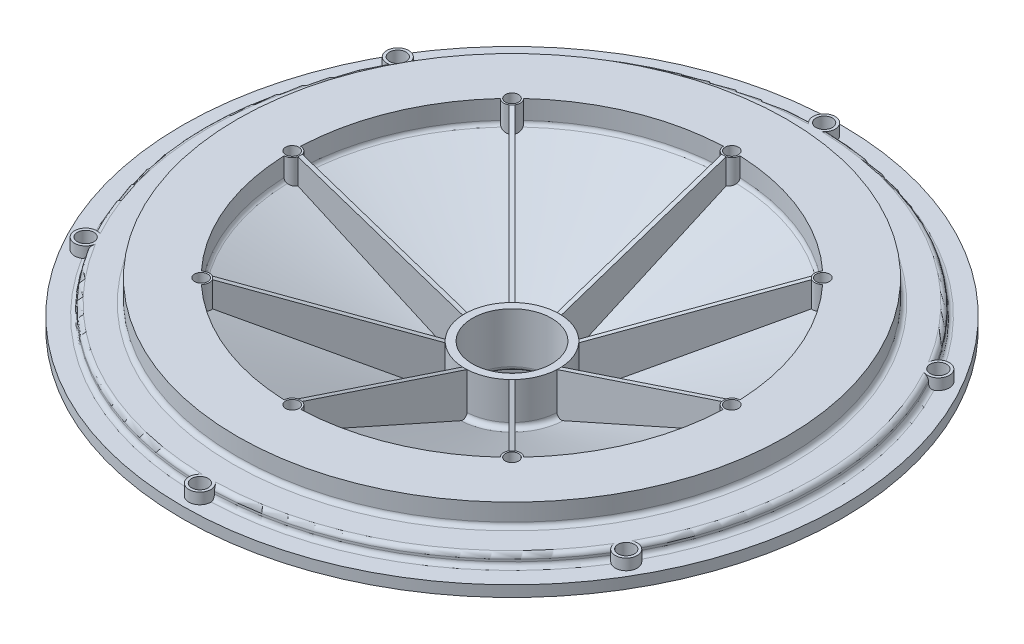
SolidWorks part; units mm, degrees
ref_plane "Front Plane" through (0, 0, 0) normal (0, 0, 1) x (1, 0, 0)
ref_plane "Top Plane" through (0, 0, 0) normal (0, 1, 0) x (1, 0, 0)
ref_plane "Right Plane" through (0, 0, 0) normal (1, 0, 0) x (0, 0, -1)
sketch "Sketch4" plane through (0, 0, 0) normal (0, 0, 1) x (1, 0, 0)
  line L0 (0, 0) -> (1.8, 0) construction
  line L1 (1.8, 2.5) -> (1.8, 0.22)
  line L2 (2, 0.02) -> (4.35, 0.02)
  line L3 (4.55, -0.18) -> (4.55, -1.95)
  line L4 (4.35, -2.15) -> (2.15, -2.15)
  line L5 (2.15, -2.15) -> (2.15, -2.3)
  line L6 (2.35, -2.5) -> (4.9, -2.5)
  line L7 (4.9, -2.5) -> (4.9, -1.2585)
  line L8 (0, 0) -> (0, 10.2137) construction
  line L9 (4.9, -1.2585) -> (4.9, 1.0489)
  line L10 (5.0186, 1.2315) -> (10.4, 3.6309)
  line L11 (1.8, 2.5) -> (2.15, 2.5)
  line L12 (2.15, 2.5) -> (2.15, 0.8082)
  line L13 (2.4314, 0.6255) -> (9.8814, 3.9471)
  line L14 (10, 4.1298) -> (10, 4.99)
  line L15 (10, 4.99) -> (12.5, 4.99)
  line L16 (12.5, 4.99) -> (12.5, 4.2)
  line L17 (12.7, 4) -> (13.8, 4)
  line L18 (14, 3.8) -> (14, 3.7)
  line L19 (14.2, 3.5) -> (15, 3.5)
  line L22 (13.5, 3) -> (13.5, 3.4309)
  line L23 (13.3, 3.6309) -> (10.4, 3.6309)
  line L24 (13.5, 3) -> (15, 3)
  line L25 (15, 3.5) -> (15, 3)
  arc A0 (2.15, 0.8082) -> (2.4314, 0.6255) centre (2.35, 0.8082) ccw
  arc A1 (4.9, 1.0489) -> (5.0186, 1.2315) centre (5.1, 1.0489) cw
  arc A2 (9.8814, 3.9471) -> (10, 4.1298) centre (9.8, 4.1298) ccw
  arc A3 (14, 3.7) -> (14.2, 3.5) centre (14.2, 3.7) ccw
  arc A4 (13.5, 3.4309) -> (13.3, 3.6309) centre (13.3, 3.4309) ccw
  arc A5 (13.8, 4) -> (14, 3.8) centre (13.8, 3.8) cw
  arc A6 (12.5, 4.2) -> (12.7, 4) centre (12.7, 4.2) ccw
  arc A7 (2.15, -2.3) -> (2.35, -2.5) centre (2.35, -2.3) ccw
  arc A8 (1.8, 0.22) -> (2, 0.02) centre (2, 0.22) ccw
  arc A9 (4.55, -1.95) -> (4.35, -2.15) centre (4.35, -1.95) cw
  arc A10 (4.35, 0.02) -> (4.55, -0.18) centre (4.35, -0.18) cw
  point P28 (2.15, 0.5)
  point P33 (10, 4)
  point P36 (14, 3.5)
  point P39 (13.5, 3.6309)
  point P46 (2.15, -2.5)
  point P51 (4.55, -2.15)
  point P54 (4.55, 0.02)
  dimension "D13" = 0.2
  dimension "D14" = 0.2
  dimension "D15" = 0.2
  dimension "D22" = 0.2
  dimension "D24" = 0.2
  dimension "D25" = 0.2
  dimension "D26" = 0.2
  dimension "D1" = 1.8
  dimension "D2" = 4.55
  dimension "D3" = 0.35
  dimension "D4" = 0.35
  dimension "D5" = 0.5
  dimension "D6" = 2
  dimension "D7" = 4
  dimension "D8" = 2.5
  dimension "D9" = 0.35
  dimension "D10" = 2.17
  dimension "D11" = 2.5
  dimension "D12" = 10
  dimension "D16" = 3
  dimension "D17" = 0.5
  dimension "D18" = 0.5
  dimension "D19" = 1
  dimension "D20" = 2.5
  dimension "D21" = 3.1
  dimension "D23" = 2.75
  dimension "D27" = 15
revolve "Revolve3" add sketch "Sketch4" angle 360 about L8
sketch "Sketch5" plane through (0, 4.99, 0) normal (0, 1, 0) x (1, 0, 0)
  line L0 (0, 10) -> (0, 0) construction
  circle A0 centre (0, 10) radius 0.375
  circle A1 centre (0, 0) radius 10 construction
  circle A2 centre (0, 0) radius 10 construction
  dimension "D1" = 0.75
  dimension "D2" = 10
extrude "Boss-Extrude1" add sketch "Sketch5" against normal up to surface (1.1571 mm away) up to face at (0, 0.6255, -2.4314)
sketch "Sketch8" plane through (0, 4, 0) normal (0, 1, 0) x (1, 0, 0)
  line L0 (0, 14.2) -> (0, 0) construction
  circle A2 centre (0, 14.2) radius 0.5
  circle A6 centre (0, 0) radius 14.2 construction
  dimension "D1" = 1
  dimension "D2" = 14.2
extrude "Boss-Extrude2" add sketch "Sketch8" against normal up to surface (0.5 mm away) up to face at (0, 3.5, -14.2)
sketch "Sketch29" plane through (0, 4.99, 0) normal (0, 1, 0) x (1, 0, 0)
  circle A0 centre (0, 10) radius 0.3
  dimension "D1" = 0.6
extrude "Cut-Extrude2" cut sketch "Sketch29" against normal blind 1
pattern_circular "CirPattern4" count 8 over 360 about axis through (0, 0, 0) along (0, -1, 0) of "Boss-Extrude1"
pattern_circular "CirPattern5" count 8 over 360 about axis through (0, 0, 0) along (0, -1, 0) of "Cut-Extrude2" reverse direction yes
sketch "Sketch35" plane through (0, 4, 0) normal (0, 1, 0) x (1, 0, 0)
  circle A0 centre (0, 14.2) radius 0.375
  dimension "D1" = 0.75
extrude "Cut-Extrude3" cut sketch "Sketch35" against normal blind 1
pattern_circular "CirPattern8" count 6 over 360 about axis through (0, 0, 0) along (0, -1, 0) of "Boss-Extrude2" reverse direction yes
pattern_circular "CirPattern10" count 6 over 360 about axis through (0, 0, 0) along (0, -1, 0) of "Cut-Extrude3"
sketch "Sketch38" plane through (0, 4.99, 0) normal (0, 1, 0) x (1, 0, 0)
  line L0 (0.1, -9.6386) -> (0.1, -2.1477)
  line L1 (-0.1, -9.6386) -> (-0.1, -2.1477)
  arc A0 (0.3749, -9.993) -> (-0.3749, -9.993) centre (0, -10) ccw construction
  circle A1 centre (0, 0) radius 2.15 construction
  arc A2 (0.3536, -9.8751) -> (-0.3536, -9.8751) centre (0, -10) ccw construction
  arc A3 (0.1, -9.6386) -> (-0.1, -9.6386) centre (0, -10) ccw
  arc A4 (0.1, -2.1477) -> (-0.1, -2.1477) centre (0, 0) cw
  point P12 (0, -9.625)
  dimension "D2" = 0.1
extrude "Boss-Extrude3" add sketch "Sketch38" against normal up to surface (1.1509 mm away) contours L1 A4 L0 A3 up to face at (0, 3.8901, 0)
sketch "Sketch39" plane through (0, 0, 0) normal (-1, 0, 0) x (0, 0, 1)
  line L0 (2.1477, 2.5) -> (9.6386, 4.99)
  line L1 (0, 0) -> (0, 7.786) construction
  line L2 (9.6386, 4.99) -> (2.1477, 4.99)
  line L3 (9.6386, 4.99) -> (2.1477, 4.99) construction
  line L4 (2.1477, 2.5) -> (2.1477, 4.99) construction
  line L5 (2.1477, 4.99) -> (2.1477, 2.5)
pattern_circular "CirPattern25" count 8 over 360 about axis through (0, 0, 0) along (0, -1, 0) of "Boss-Extrude3" reverse direction yes
revolve "Cut-Revolve1" cut sketch "Sketch39" angle 360 about L1
scale "Scale1" scale about centroid uniform scaling yes scale factor 5
